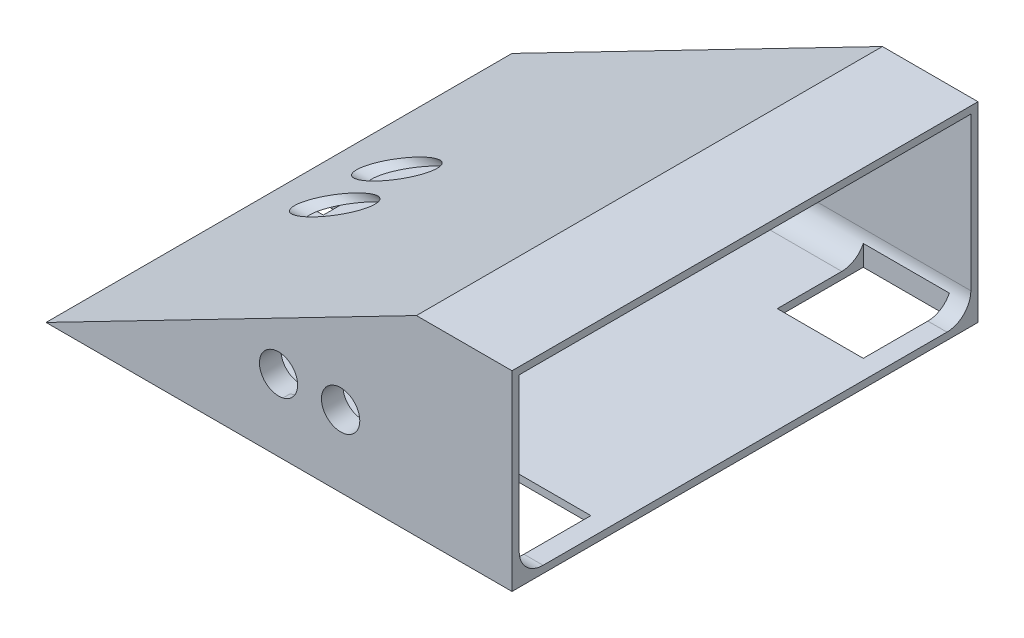
SolidWorks part; units mm, degrees
ref_plane "Front Plane" through (0, 0, 0) normal (0, 0, 1) x (1, 0, 0)
ref_plane "Top Plane" through (0, 0, 0) normal (0, 1, 0) x (1, 0, 0)
ref_plane "Right Plane" through (0, 0, 0) normal (1, 0, 0) x (0, 0, -1)
ref_plane "Plane1" through (0, 0, 0) normal (1, 0, 0) x (0, 0, -1)
ref_plane "Plane2" through (0, 0, 97.5) normal (0, 0, 1) x (1, 0, 0)
ref_plane "Plane3" through (52, 0, 0) normal (1, 0, 0) x (0, 0, -1)
sketch "Sketch2" plane through (0, 0, 0) normal (0, 0, 1) x (1, 0, 0)
  line L0 (0, 0) -> (195, 0)
  line L1 (195, 0) -> (195, 80)
  line L2 (195, 80) -> (155, 80)
  line L3 (155, 80) -> (0, 0)
  dimension "D1" = 195
  dimension "D2" = 40
  dimension "80" = 80
extrude "Robot" add sketch "Sketch2" along normal blind 195
sketch "Sketch3" plane through (0, 0, 195) normal (0, 0, 1) x (1, 0, 0)
  line L0 (0, 0) -> (195, 0) construction
  circle A0 centre (97.2899, 30) radius 8.02
  circle A1 centre (123.2899, 30) radius 8.02
  dimension "D1" = 30
  dimension "D2" = 16.04
  dimension "D4" = 16.04
  dimension "D3" = 26
  dimension "D5" = 30
sketch "Arriba" plane through (0, 80, 0) normal (0, 1, 0) x (1, 0, 0)
  line L0 (195, 0) -> (195, -195) construction
  line L1 (0, 0) -> (0, -195) construction
  line L2 (0, -97.5) -> (195, -97.5) construction
  line L3 (0, 0) -> (195, 0) construction
  line L4 (0, -195) -> (195, -195) construction
  line L5 (97.5, 0) -> (97.5, -195) construction
sketch "Adelante" plane through (0, 0, 0) normal (1, 0, 0) x (0, 0, -1)
  line L0 (0, 80) -> (0, 0) construction
  line L1 (-97.5, 80) -> (-97.5, 0) construction
  line L2 (0, 80) -> (-195, 80) construction
  line L3 (-195, 0) -> (0, 0) construction
  line L4 (-195, 80) -> (-195, 0) construction
  line L5 (0, 0) -> (-195, 0) construction
sketch "Sketch9" plane through (0, 0, 0) normal (0, 0, -1) x (-1, 0, 0)
  line L1 (0, 0) -> (-195, 0) construction
  circle A0 centre (-97.284, 30) radius 8.2
  circle A1 centre (-123.284, 30) radius 8.2
  dimension "D2" = 16.4
  dimension "D4" = 30
  dimension "D6" = 16.4
  dimension "D3" = 30
  dimension "D5" = 26
sketch "Sketch10" plane through (0, 0, 0) normal (0, -1, 0) x (-1, 0, 0)
  line L0 (0, -195) -> (-195, -195) construction
  line L1 (-187, -191) -> (-150, -191)
  line L2 (-187, -191) -> (-187, -154)
  line L3 (-187, -154) -> (-150, -154)
  line L4 (-150, -191) -> (-150, -154)
  line L5 (-195, 0) -> (-195, -195) construction
  dimension "D1" = 4
  dimension "D2" = 8
  dimension "D3" = 37
  dimension "D4" = 37
sketch "Sketch12" plane through (0, 0, 0) normal (0, -1, 0) x (-1, 0, 0)
  line L0 (-195, 0) -> (-195, -195) construction
  line L1 (-187, -40) -> (-151, -40)
  line L2 (-187, -40) -> (-187, -4)
  line L3 (-187, -4) -> (-151, -4)
  line L4 (-151, -40) -> (-151, -4)
  line L5 (0, 0) -> (-195, 0) construction
  dimension "D1" = 8
  dimension "D2" = 4
  dimension "D3" = 36
  dimension "D4" = 36
sketch "Sketch13" plane through (0, 0, 0) normal (0, -1, 0) x (1, 0, 0)
  line L0 (0, 0) -> (195, 0) construction
  line L1 (15, 8) -> (22.1, 8)
  line L2 (15, 8) -> (15, 15.1)
  line L3 (15, 15.1) -> (22.1, 15.1)
  line L4 (22.1, 8) -> (22.1, 15.1)
  line L5 (0, 0) -> (0, 195) construction
  dimension "D1" = 8
  dimension "D2" = 15
  dimension "D3" = 7.1
  dimension "D4" = 7.1
sketch "Sketch14" plane through (0, 0, 0) normal (0, -1, 0) x (-1, 0, 0)
  line L0 (0, -195) -> (-195, -195) construction
  line L1 (-15, -179.9) -> (-22.1, -179.9)
  line L2 (-15, -179.9) -> (-15, -187)
  line L3 (-15, -187) -> (-22.1, -187)
  line L4 (-22.1, -179.9) -> (-22.1, -187)
  line L5 (0, 0) -> (0, -195) construction
  dimension "D1" = 8
  dimension "D2" = 15
  dimension "D3" = 7.1
  dimension "D4" = 7.1
sketch "Sketch15" plane through (0, 0, 0) normal (0, -1, 0) x (-1, 0, 0)
  line L0 (0, -97.5) -> (-195, -97.5) construction
  line L1 (-15, -93.95) -> (-22.1, -93.95)
  line L2 (-15, -93.95) -> (-15, -101.05)
  line L3 (-15, -101.05) -> (-22.1, -101.05)
  line L4 (-22.1, -93.95) -> (-22.1, -101.05)
  line L5 (0, 0) -> (0, -195) construction
  dimension "D1" = 3.55
  dimension "D2" = 3.55
  dimension "D3" = 7.1
  dimension "D4" = 15
shell "Vacio por dentro 3mm" thickness 3 removed face at (195, 40, 97.5)
extrude "Ultrasonico Derecha" cut sketch "Sketch3" against normal blind 3
sketch "Ultrasonico Centro " plane through (0, 0, 0) normal (1, 0, 0) x (0, 0, -1)
  line L0 (0, 0) -> (-195, 0) construction
  line L1 (-97.5, 80) -> (-97.5, 0) construction
  circle A0 centre (-85, 19) radius 8.7
  circle A1 centre (-111, 19) radius 8.7
  dimension "D2" = 17.4
  dimension "D4" = 17.4
  dimension "D1" = 19
  dimension "D3" = 12.5
  dimension "D5" = 13.5
  dimension "D6" = 19
extrude "Ultrasonico Izquierda" cut sketch "Sketch9" against normal blind 3
extrude "Rueda Derecha" cut sketch "Sketch10" against normal blind 3
extrude "Rueda Izquierda" cut sketch "Sketch12" against normal blind 3
extrude "Cyn70 Derecha" cut sketch "Sketch14" against normal blind 4
extrude "Cny70 Centro" cut sketch "Sketch15" against normal blind 4
extrude "Cny70 Izquierda" cut sketch "Sketch13" against normal blind 4
extrude "Cut-Extrude4" cut sketch "Ultrasonico Centro " along normal blind 75
fillet "Fillet2" radius 10 2 edges at (103.6768, 3, 3) (103.6768, 3, 192)
sketch "Sketch16" plane through (0, 0, 195) normal (0, 0, 1) x (1, 0, 0)
  circle A0 centre (123.2899, 30) radius 8.02
  circle A1 centre (123.2899, 30) radius 8.6857
  circle A2 centre (97.3351, 30.0107) radius 8.6857
  circle A3 centre (97.3351, 30.0107) radius 8.02
extrude "Boss-Extrude1" add sketch "Sketch16" against normal blind 9
mirror "Mirror1" about plane through (0, 0, 97.5) normal (0, 0, 1) of "Boss-Extrude1"
